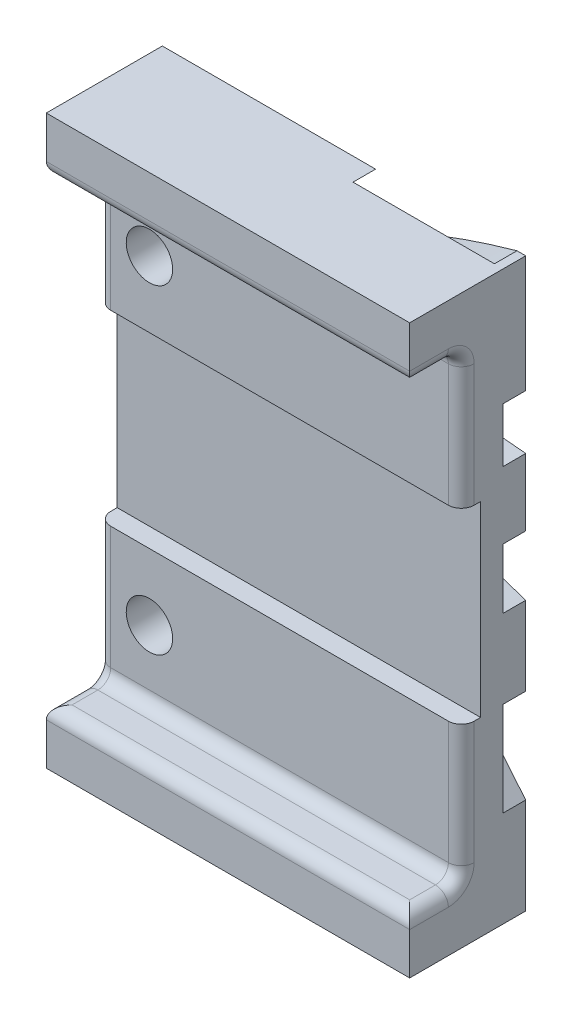
SolidWorks part; units mm, degrees
ref_plane "Front Plane" through (0, 0, 0) normal (0, 0, 1) x (1, 0, 0)
ref_plane "Top Plane" through (0, 0, 0) normal (0, 1, 0) x (1, 0, 0)
ref_plane "Right Plane" through (0, 0, 0) normal (1, 0, 0) x (0, 0, -1)
sketch "Sketch1" plane through (0, 0, 0) normal (0, 0, 1) x (1, 0, 0)
  line L1 (-14.09, -22) -> (14.09, -22)
  line L2 (-14.09, -22) -> (-14.09, 22)
  line L3 (-14.09, 22) -> (14.09, 22)
  line L4 (14.09, -22) -> (14.09, 22)
  line L5 (-14.09, -22) -> (14.09, 22) construction
  line L6 (-14.09, 22) -> (14.09, -22) construction
  point P0 (0, 0)
  dimension "D1" = 44
  dimension "D2" = 28.18
extrude "Boss-Extrude1" add sketch "Sketch1" along normal blind 11 and the other way blind 2
sketch "Sketch3" plane through (-14.09, 0, 0) normal (-1, 0, 0) x (0, 0, 1)
  line L0 (8, 7.25) -> (11, 7.25)
  line L5 (8, 17.75) -> (3, 17.75)
  line L6 (8, 17.75) -> (8, 7.25)
  line L7 (8, -17.75) -> (3, -17.75)
  line L8 (3, 17.75) -> (3, 7.25)
  line L9 (11, -7.25) -> (8, -7.25)
  line L10 (8, -7.25) -> (8, -17.75)
  line L13 (3, -7.25) -> (1.5034, -7.25)
  line L14 (11, 7.25) -> (11, -7.25)
  line L15 (14.8907, 0) -> (-5.9971, 0) construction
  line L16 (3, 7.25) -> (1.5034, 7.25)
  line L17 (1.5034, 7.25) -> (1.5034, -7.25)
  line L18 (3, -7.25) -> (3, -17.75)
  dimension "D1" = 3
  dimension "D2" = 5
  dimension "D3" = 35.5
extrude "Cut-Extrude1" cut sketch "Sketch3" against normal blind 37
sketch "Sketch4" plane through (0, -22, 0) normal (0, -1, 0) x (1, 0, 0)
  line L0 (-14.09, 11) -> (14.09, 11) construction
  line L1 (-6.09, 11) -> (14.09, 11)
  line L2 (-6.09, 11) -> (-6.09, 7)
  line L3 (-6.09, 7) -> (14.09, 7)
  line L4 (14.09, 11) -> (14.09, 7)
  line L5 (14.09, -2) -> (14.09, 11) construction
  line L6 (-14.09, -2) -> (-14.09, 11) construction
  dimension "D1" = 4
  dimension "D2" = 8
extrude "Cut-Extrude2" cut sketch "Sketch4" against normal blind 48
sketch "Sketch5" plane through (0, 0, -2) normal (0, 0, -1) x (-1, 0, 0)
  line L0 (14.09, 4.4317) -> (14.09, 4.2995)
  line L1 (-14.09, 22) -> (14.09, 22) construction
  line L2 (-2.4482, 22) -> (-13.4131, 22)
  line L3 (14.09, 4.4317) -> (14.09, 4.2995)
  line L4 (5.5922, -22) -> (0.0012, -22)
  line L5 (-14.09, 12.9435) -> (-14.09, 8.7272)
  line L6 (-2.4482, 22) -> (-13.4131, 22)
  line L7 (5.5922, -22) -> (0.0012, -22)
  line L8 (-5.5133, -22) -> (-9.4224, -22)
  line L9 (-14.09, 12.9435) -> (-14.09, 8.7272)
  line L10 (-14.09, 3.5233) -> (-14.09, -1.1313)
  line L11 (-14.09, -7.2405) -> (-14.09, -14.5457)
  line L12 (-5.5133, -22) -> (-9.4224, -22)
  line L13 (14.09, 22) -> (14.09, -22) construction
  line L14 (14.09, -22) -> (-14.09, -22) construction
  line L15 (-14.09, -22) -> (-14.09, 22) construction
  spline S0 degree 3 poles (-2.4482, 22) (19.5671, 11.5364) (5.1516, -7.6222) (5.5922, -22) knots 0 0 0 0 0.832841 0.832841 0.832841 0.832841
  spline S1 degree 3 poles (-13.4131, 22) (18.4961, 13.0475) (3.5462, -4.8632) (0.0012, -22) knots 0 0 0 0 0.886772 0.886772 0.886772 0.886772
  spline S2 degree 3 poles (-14.09, 12.9435) (17.0272, 14.2309) (-0.9132, -5.6377) (-5.5133, -22) knots 0 0 0 0 0.882154 0.882154 0.882154 0.882154
  spline S3 degree 3 poles (-14.09, 8.7272) (12.7104, 11.6786) (-5.2505, -7.0269) (-9.4224, -22) knots 0 0 0 0 0.871233 0.871233 0.871233 0.871233
  spline S4 degree 2 poles (-14.09, 3.5233) (7.9134, 11.6377) (-14.09, -14.5457) knots 0 0 0 1 1 1
  spline S5 degree 2 poles (-14.09, -1.1313) (-1.6541, 3.2119) (-14.09, -7.2405) knots 0 0 0 1 1 1
  line M1 (-14.09, 22) -> (-14.09, -22)
  line M2 (-14.09, -22) -> (14.09, -22)
  line M4 (14.09, 22) -> (-14.09, 22)
extrude "Cut-Extrude3" cut sketch "Sketch5" against normal blind 1.75 contours S3 S2 M1 M2 | S5 S4 M1 | S1 S0 M4 M2 region at (-9.2495, 2.4628, -2) region at (7.4678, -21.6069, -2) region at (4.526, -0.8216, -2)
sketch "Sketch7" plane through (0, 0, 11) normal (0, 0, 1) x (1, 0, 0)
  line L3 (-31.6118, 0) -> (31.371, 0) construction
  line L4 (-10.09, 22.9416) -> (-10.09, 7.5663) construction
  line L5 (-6.09, 22) -> (-6.09, 7.25) construction
  line L6 (-14.09, 22) -> (-14.09, 7.25) construction
  circle A0 centre (-10.09, 12.4) radius 1.8
  circle A1 centre (-10.09, -12.4) radius 1.8
  dimension "D1" = 3.6
  dimension "D2" = 24.8
extrude "Cut-Extrude4" cut sketch "Sketch7" against normal blind 23
sketch "Sketch10" plane through (0, 22, 0) normal (0, 1, 0) x (1, 0, 0)
  line L1 (-4.8142, -11.586) -> (-16.61, -11.586)
  line L2 (-4.8142, -11.586) -> (-4.8142, -7)
  line L3 (-4.8142, -7) -> (-16.61, -7)
  line L4 (-16.61, -11.586) -> (-16.61, -7)
  line L5 (14.09, -7) -> (-6.09, -7) construction
extrude "Cut-Extrude7" cut sketch "Sketch10" against normal blind 53
fillet "Fillet1" radius 1 12 edges at (-14.09, -12.5, 3) (14.09, -12.5, 3) (14.09, 12.5, 3) (-14.09, 12.5, 3) (-14.09, -17.75, 5) (0, -17.75, 3) (14.09, -17.75, 5) (0, -17.75, 7) (14.09, 17.75, 5) (0, 17.75, 3) (-14.09, 17.75, 5) (0, 17.75, 7)
sketch "Sketch8" plane through (0, 0, -2) normal (0, 0, -1) x (-1, 0, 0)
  circle A0 centre (10.09, -12.4) radius 3.25
  circle A1 centre (10.09, 12.4) radius 3.25
  dimension "D1" = 6.5
extrude "Cut-Extrude5" cut sketch "Sketch8" against normal blind 1.75
